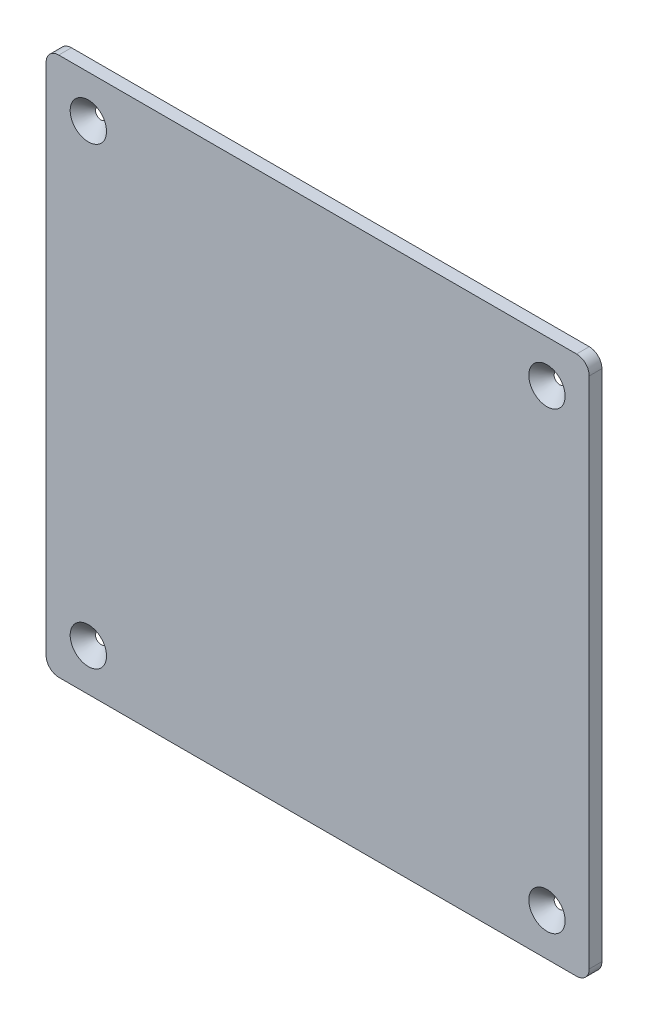
SolidWorks part; units mm, degrees
ref_plane "Спереди" through (0, 0, 0) normal (0, 0, 1) x (1, 0, 0)
ref_plane "Сверху" through (0, 0, 0) normal (0, 1, 0) x (1, 0, 0)
ref_plane "Справа" through (0, 0, 0) normal (1, 0, 0) x (0, 0, -1)
sketch "Эскиз1" plane through (0, 0, 0) normal (0, 0, 1) x (1, 0, 0)
  line L8 (-64.25, 60.75) -> (-64.25, -60.75)
  line L9 (-61.25, -63.75) -> (61.25, -63.75)
  line L10 (64.25, -60.75) -> (64.25, 60.75)
  line L11 (61.25, 63.75) -> (-61.25, 63.75)
  arc A8 (-61.25, 63.75) -> (-64.25, 60.75) centre (-61.25, 60.75) ccw
  arc A9 (-64.25, -60.75) -> (-61.25, -63.75) centre (-61.25, -60.75) ccw
  arc A10 (61.25, -63.75) -> (64.25, -60.75) centre (61.25, -60.75) ccw
  arc A11 (64.25, 60.75) -> (61.25, 63.75) centre (61.25, 60.75) ccw
extrude "Бобышка-Вытянуть1" add sketch "Эскиз1" along normal blind 3
sketch "Эскиз2" plane through (0, 0, 0) normal (0, 0, -1) x (-1, 0, 0)
  line L33 (58.25, -43.75) -> (58.25, 43.75)
  line L34 (44.25, 57.75) -> (-44.25, 57.75)
  line L35 (-58.25, 43.75) -> (-58.25, -43.75)
  line L36 (-44.25, -57.75) -> (44.25, -57.75)
  arc A79 (44.25, -57.75) -> (48.25, -53.75) centre (44.25, -53.75) ccw
  arc A80 (54.25, -47.75) -> (48.25, -53.75) centre (54.25, -53.75) ccw
  arc A81 (54.25, -47.75) -> (58.25, -43.75) centre (54.25, -43.75) ccw
  arc A82 (58.25, 43.75) -> (54.25, 47.75) centre (54.25, 43.75) ccw
  arc A83 (48.25, 53.75) -> (54.25, 47.75) centre (54.25, 53.75) ccw
  arc A84 (48.25, 53.75) -> (44.25, 57.75) centre (44.25, 53.75) ccw
  arc A85 (-44.25, 57.75) -> (-48.25, 53.75) centre (-44.25, 53.75) ccw
  arc A86 (-54.25, 47.75) -> (-48.25, 53.75) centre (-54.25, 53.75) ccw
  arc A87 (-54.25, 47.75) -> (-58.25, 43.75) centre (-54.25, 43.75) ccw
  arc A88 (-58.25, -43.75) -> (-54.25, -47.75) centre (-54.25, -43.75) ccw
  arc A89 (-48.25, -53.75) -> (-54.25, -47.75) centre (-54.25, -53.75) ccw
  arc A90 (-48.25, -53.75) -> (-44.25, -57.75) centre (-44.25, -53.75) ccw
extrude "Вытянуть-Тонкостенный1" add sketch "Эскиз2" along normal blind 2 thin thin type one direction reverse wall 3
sketch "Эскиз3" plane through (0, 0, 3) normal (0, 0, 1) x (1, 0, 0)
  circle A4 centre (54.25, -53.75) radius 1.3
  circle A5 centre (54.25, 53.75) radius 1.3
  circle A6 centre (-54.25, 53.75) radius 1.3
  circle A7 centre (-54.25, -53.75) radius 1.3
extrude "Вырез-Вытянуть1" cut sketch "Эскиз3" against normal blind 5
chamfer "Фаска1" distance 3 angle 45 4 edges at (55.55, -53.75, 3) (55.55, 53.75, 3) (-52.95, 53.75, 3) (-52.95, -53.75, 3)
sketch "Эскиз5" plane through (0, 0, 0) normal (0, 0, -1) x (-1, 0, 0)
  line L4 (-44.25, -54.75) -> (44.25, -54.75)
  line L5 (55.25, -43.75) -> (55.25, 43.75)
  line L6 (44.25, 54.75) -> (-44.25, 54.75)
  line L7 (-55.25, 43.75) -> (-55.25, -43.75)
  line L8 (-44.25, -54.75) -> (44.25, -54.75)
  line L9 (55.25, -43.75) -> (55.25, 43.75)
  line L10 (44.25, 54.75) -> (-44.25, 54.75)
  line L11 (-55.25, 43.75) -> (-55.25, -43.75)
  arc A12 (44.25, -54.75) -> (45.25, -53.75) centre (44.25, -53.75) ccw
  arc A13 (54.25, -44.75) -> (45.25, -53.75) centre (54.25, -53.75) ccw
  arc A14 (54.25, -44.75) -> (55.25, -43.75) centre (54.25, -43.75) ccw
  arc A15 (55.25, 43.75) -> (54.25, 44.75) centre (54.25, 43.75) ccw
  arc A16 (45.25, 53.75) -> (54.25, 44.75) centre (54.25, 53.75) ccw
  arc A17 (45.25, 53.75) -> (44.25, 54.75) centre (44.25, 53.75) ccw
  arc A18 (-44.25, 54.75) -> (-45.25, 53.75) centre (-44.25, 53.75) ccw
  arc A19 (-54.25, 44.75) -> (-45.25, 53.75) centre (-54.25, 53.75) ccw
  arc A20 (-54.25, 44.75) -> (-55.25, 43.75) centre (-54.25, 43.75) ccw
  arc A21 (-55.25, -43.75) -> (-54.25, -44.75) centre (-54.25, -43.75) ccw
  arc A22 (-45.25, -53.75) -> (-54.25, -44.75) centre (-54.25, -53.75) ccw
  arc A23 (-45.25, -53.75) -> (-44.25, -54.75) centre (-44.25, -53.75) ccw
  arc A24 (44.25, -54.75) -> (45.25, -53.75) centre (44.25, -53.75) ccw
  arc A25 (54.25, -44.75) -> (45.25, -53.75) centre (54.25, -53.75) ccw
  arc A26 (54.25, -44.75) -> (55.25, -43.75) centre (54.25, -43.75) ccw
  arc A27 (55.25, 43.75) -> (54.25, 44.75) centre (54.25, 43.75) ccw
  arc A28 (45.25, 53.75) -> (54.25, 44.75) centre (54.25, 53.75) ccw
  arc A29 (45.25, 53.75) -> (44.25, 54.75) centre (44.25, 53.75) ccw
  arc A30 (-44.25, 54.75) -> (-45.25, 53.75) centre (-44.25, 53.75) ccw
  arc A31 (-54.25, 44.75) -> (-45.25, 53.75) centre (-54.25, 53.75) ccw
  arc A32 (-54.25, 44.75) -> (-55.25, 43.75) centre (-54.25, 43.75) ccw
  arc A33 (-55.25, -43.75) -> (-54.25, -44.75) centre (-54.25, -43.75) ccw
  arc A34 (-45.25, -53.75) -> (-54.25, -44.75) centre (-54.25, -53.75) ccw
  arc A35 (-45.25, -53.75) -> (-44.25, -54.75) centre (-44.25, -53.75) ccw
  dimension "D1" = 0
